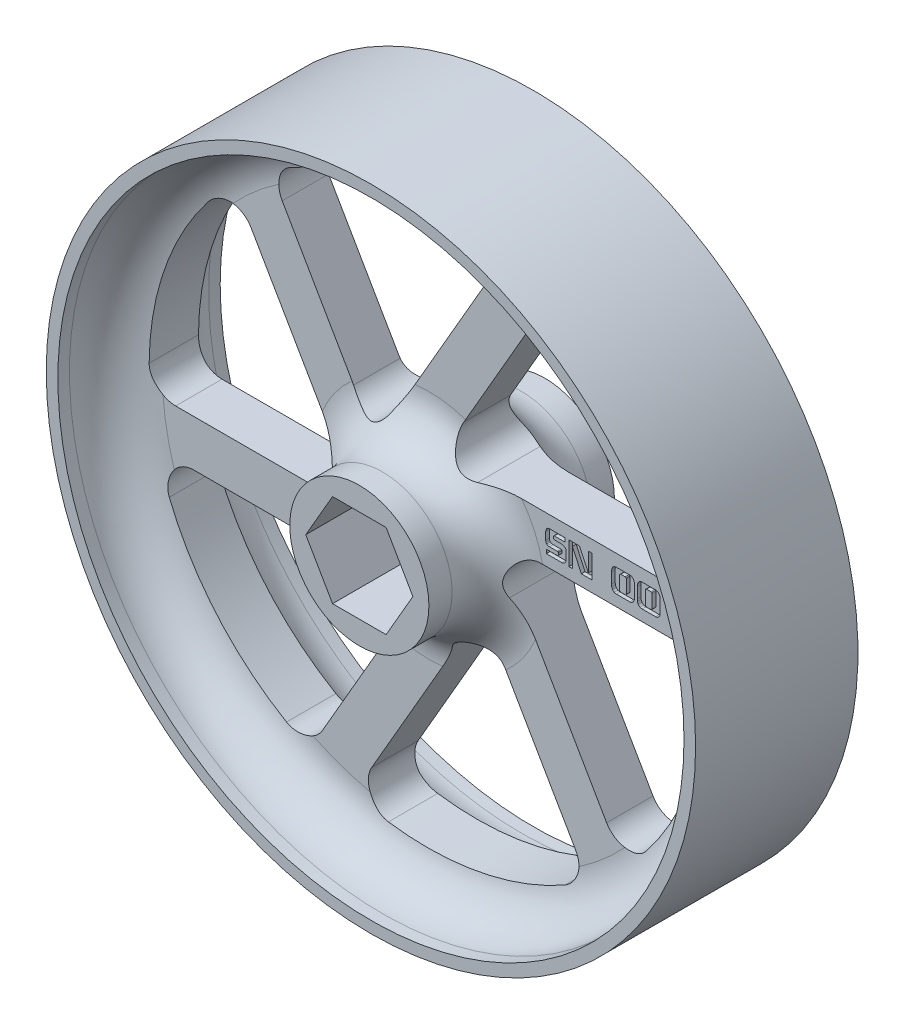
SolidWorks part; units mm, degrees
material "6061-T6 (SS)"
ref_plane "Front Plane" through (0, 0, 0) normal (0, 0, 1) x (1, 0, 0)
ref_plane "Top Plane" through (0, 0, 0) normal (0, 1, 0) x (1, 0, 0)
ref_plane "Right Plane" through (0, 0, 0) normal (1, 0, 0) x (0, 0, -1)
sketch "Sketch1" plane through (0, 0, 0) normal (0, 0, 1) x (1, 0, 0)
  line L1 (3.6662, -6.35) -> (7.3323, 0)
  line L2 (7.3323, 0) -> (3.6662, 6.35)
  line L3 (3.6662, 6.35) -> (-3.6662, 6.35)
  line L4 (-3.6662, 6.35) -> (-7.3323, 0)
  line L5 (-7.3323, 0) -> (-3.6662, -6.35)
  line L6 (-3.6662, -6.35) -> (3.6662, -6.35)
  circle A0 centre (0, 0) radius 44.45
  circle A1 centre (0, 0) radius 6.35 construction
  dimension "D1" = 88.9
  dimension "D2" = 12.7
extrude "Boss-Extrude1" add sketch "Sketch1" along normal mid plane 25.4
sketch "Sketch2" plane through (0, 0, 0) normal (0, 1, 0) x (1, 0, 0)
  line L0 (0, -1000) -> (0, 49000) construction
  line L1 (-1000, 0) -> (49000, 0) construction
  line L2 (-36.5125, 3.175) -> (-15.875, 3.175)
  line L3 (-42.8625, 9.525) -> (-42.8625, 12.7)
  line L4 (44.45, 12.7) -> (-44.45, 12.7) construction
  line L5 (-44.45, 12.7) -> (-44.45, -12.7) construction
  line L6 (-9.525, 9.525) -> (-9.525, 12.7)
  line L7 (-9.525, 12.7) -> (-42.8625, 12.7)
  arc A0 (-42.8625, 9.525) -> (-36.5125, 3.175) centre (-36.5125, 9.525) ccw
  arc A1 (-15.875, 3.175) -> (-9.525, 9.525) centre (-15.875, 9.525) ccw
  dimension "D1" = 12.7
  dimension "D2" = 6.35
  dimension "D3" = 1.5875
  dimension "D4" = 19.05
revolve "Cut-Revolve1" cut sketch "Sketch2" angle 360 about L0
mirror "Mirror1" about plane through (0, 0, 0) normal (0, 0, 1) of "Cut-Revolve1"
sketch "Sketch3" plane through (0, 0, 12.7) normal (0, 0, 1) x (1, 0, 0)
  circle A0 centre (0, 0) radius 27.1324
extrude "Cut-Extrude1" cut sketch "Sketch3" against normal blind 1.5875 flip side to cut
mirror "Mirror2" about plane through (0, 0, 0) normal (0, 0, 1) of "Cut-Extrude1"
sketch "Sketch4" plane through (0, 0, 3.175) normal (0, 0, 1) x (1, 0, 0)
  line L0 (0, 9.525) -> (29.3743, 9.525) construction
  line L1 (15.1046, 3.175) -> (34.6701, 3.175)
  line L2 (12.135, -1.9685) -> (24.3289, -23.089)
  arc A0 (29.9984, -23.4884) -> (38.099, -0.2791) centre (0, 0) ccw
  circle A1 centre (0, 0) radius 9.525 construction
  arc A2 (12.135, -1.9685) -> (15.1046, 3.175) centre (15.1046, -0.254) cw
  circle A3 centre (0, 0) radius 9.525 construction
  circle A4 centre (0, 0) radius 44.45 construction
  arc A5 (24.3289, -23.089) -> (29.9984, -23.4884) centre (27.2985, -21.3745) ccw
  arc A6 (34.6701, 3.175) -> (38.099, -0.2791) centre (34.6701, -0.254) cw
  dimension "D4" = 6.35
  dimension "D2" = 3.429
  dimension "D1" = 6.35
  dimension "D3" = 60
extrude "Cut-Extrude2" cut sketch "Sketch4" against normal through all both and the other way through all
pattern_circular "CirPattern1" count 6 over 360 about axis through (0, 0, -1000) along (0, 0, -1) of "Cut-Extrude2"
sketch "Sketch5" plane through (0, 0, 3.175) normal (0, 0, 1) x (1, 0, 0)
  text T0 "SN 001" font "Enter Sansman" height 3.175
extrude "Cut-Extrude3" cut sketch "Sketch5" against normal blind 0.508
